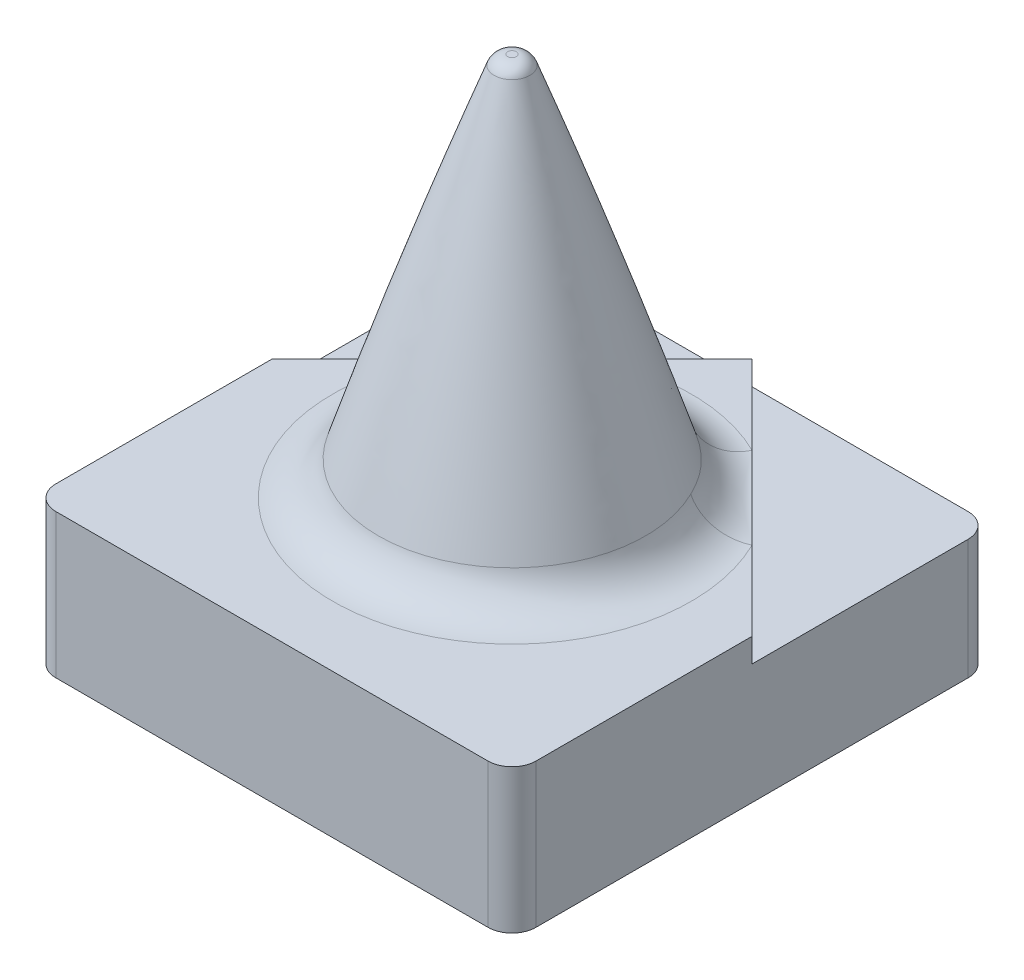
SolidWorks part; units mm, degrees
ref_plane "Plan de face" through (0, 0, 0) normal (0, 0, 1) x (1, 0, 0)
ref_plane "Plan de dessus" through (0, 0, 0) normal (0, 1, 0) x (1, 0, 0)
ref_plane "Plan de droite" through (0, 0, 0) normal (1, 0, 0) x (0, 0, -1)
sketch "Esquisse1" plane through (0, 0, 0) normal (0, 1, 0) x (1, 0, 0)
  line L1 (-5, -5) -> (5, -5)
  line L2 (-5, -5) -> (-5, 5)
  line L3 (-5, 5) -> (5, 5)
  line L4 (5, -5) -> (5, 5)
  line L5 (-5, -5) -> (5, 5) construction
  line L6 (-5, 5) -> (5, -5) construction
  point P0 (0, 0)
  dimension "D1" = 10
  dimension "D2" = 10
extrude "Boss.-Extru.1" add sketch "Esquisse1" along normal blind 3
sketch "Esquisse2" plane through (0, 3, 0) normal (0, 1, 0) x (1, 0, 0)
  line L0 (-5, 0) -> (0, 5)
  line L1 (-5, 5) -> (-5, -5) construction
  line L2 (5, 5) -> (-5, 5) construction
  line L3 (0, 5) -> (5, 0)
  line L4 (5, -5) -> (5, 5) construction
  line L5 (5, 0) -> (5, 5)
  line L6 (5, 5) -> (-5, 5)
  line L7 (-5, 5) -> (-5, 0)
  line M1 (5, -5) -> (5, 5)
  line M2 (5, 5) -> (-5, 5)
  line M3 (-5, 5) -> (-5, -5)
extrude "Enlèv. mat.-Extru.1" cut sketch "Esquisse2" against normal blind 0.5 contours L0 M3 M2 | L3 M2 M1 region at (-3.3333, 3, -3.3333) region at (3.3333, 3, -3.3333)
sketch "Esquisse4" plane through (0, 0, 0) normal (0, 0, 1) x (1, 0, 0)
  line L0 (-5, 3) -> (5, 3) construction
  line L1 (0, 11) -> (0, 3)
  line L2 (0, 3) -> (3, 3)
  line L3 (0.3, 11) -> (0, 11)
  spline S0 degree 2 poles (3, 3) (1.7575, 7.0363) (0.3, 11) knots 0 0 0 1 1 1
  dimension "D1" = 3
  dimension "D2" = 8
  dimension "D3" = 0.3
revolve "Révolution1" add sketch "Esquisse4" angle 360 about L1
fillet "Congé2" radius 0.3 1 edges at (-0.3, 11, 0)
fillet "Congé3" radius 0.5 4 edges at (-5, 1.25, -5) (5, 1.25, -5) (5, 1.5, 5) (-5, 1.5, 5)
sketch "Esquisse5" plane through (0, 0, 0) normal (0, 0, 1) x (1, 0, 0)
  line L0 (5, 3) -> (5, 0) construction
  line L1 (0, 8.5) -> (0, 0)
  line L2 (0, 0) -> (3.5, 0)
  line L3 (0.4, 8.5) -> (0, 8.5)
  line L4 (-4.5, 0) -> (4.5, 0) construction
  spline S0 degree 3 poles (3.5, 0) (2.6918, 0.7563) (2.9025, 1.1626) (1.2817, 5.9433) (0.8226, 7.1232) (0.4, 8.5) knots 0 0 0 0 0.197893 0.297893 1 1 1 1
  dimension "D1" = 3.5
  dimension "D2" = 8.5
  dimension "D3" = 0.4
  dimension "D4" = 0
  dimension "D5" = 2
  dimension "D6" = 5
  dimension "D7" = 2.4
revolve "Enlèvement de matière-Révolution1" cut sketch "Esquisse5" angle 360 about L1
fillet "Congé4" radius 1 1 edges at (-3, 3, 0)
